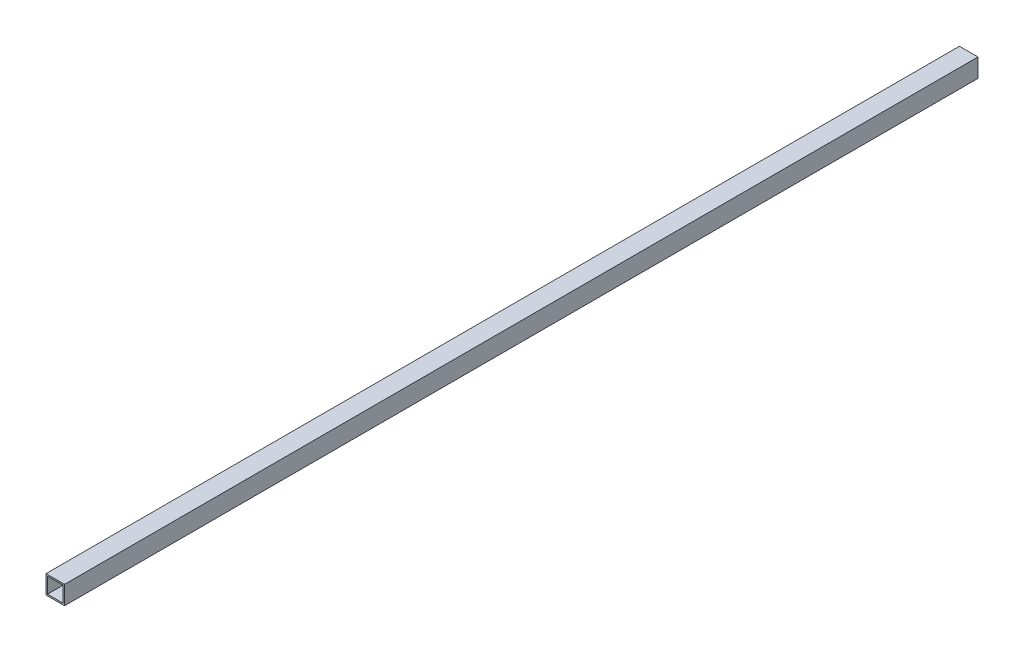
SolidWorks part; units mm, degrees
ref_plane "前基準面" through (0, 0, 0) normal (0, 0, 1) x (1, 0, 0)
ref_plane "上基準面" through (0, 0, 0) normal (0, 1, 0) x (1, 0, 0)
ref_plane "右基準面" through (0, 0, 0) normal (1, 0, 0) x (0, 0, -1)
sketch "草圖1" plane through (0, 0, 0) normal (0, 0, 1) x (1, 0, 0)
  line L0 (-10.7, 10.7) -> (10.7, 10.7)
  line L1 (-12.7, 12.7) -> (12.7, 12.7)
  line L2 (-12.7, 12.7) -> (-12.7, -12.7)
  line L3 (-12.7, -12.7) -> (12.7, -12.7)
  line L4 (12.7, 12.7) -> (12.7, -12.7)
  line L5 (-12.7, 12.7) -> (12.7, -12.7) construction
  line L6 (-12.7, -12.7) -> (12.7, 12.7) construction
  line L7 (10.7, 10.7) -> (10.7, -10.7)
  line L8 (-10.7, -10.7) -> (10.7, -10.7)
  line L9 (-10.7, 10.7) -> (-10.7, -10.7)
  point P0 (0, 0)
  dimension "D1" = 25.4
  dimension "D2" = 25.4
  dimension "D3" = 2
extrude "填料-伸長1" add sketch "草圖1" along normal blind 1250 contours L1 L4 L3 L2
extrude "除料-伸長1" cut sketch "草圖1<3>" along normal through all contours L0 L7 L8 L9
sketch "草圖1<3>" plane through (0, 0, 0) normal (0, 0, 1) x (1, 0, 0) same geometry as "草圖1"
